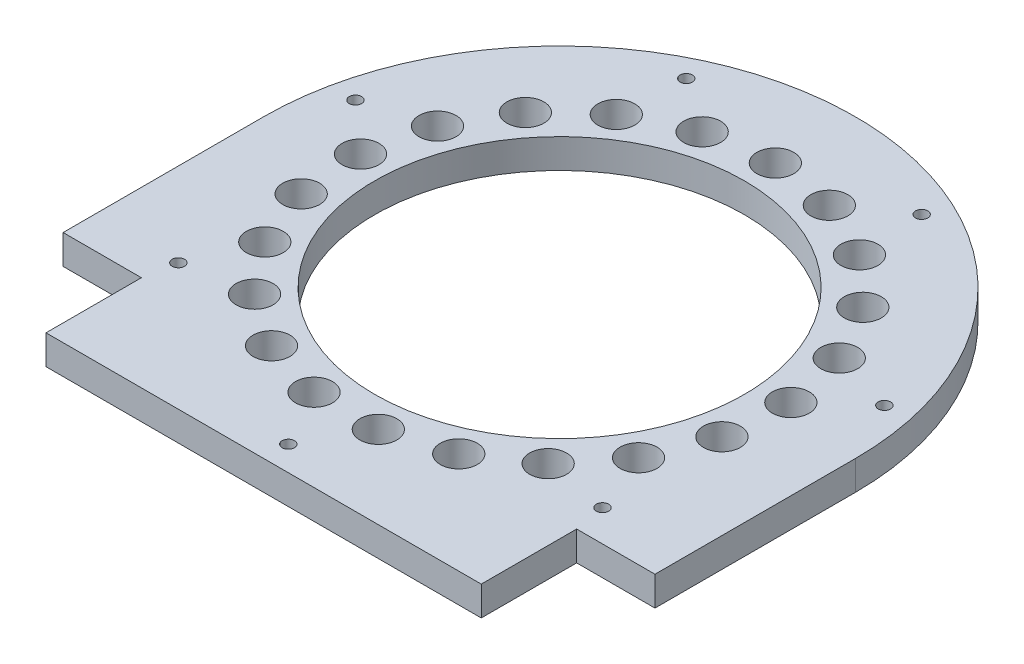
SolidWorks part; units mm, degrees
ref_plane "Front Plane" through (0, 0, 0) normal (0, 0, 1) x (1, 0, 0)
ref_plane "Top Plane" through (0, 0, 0) normal (0, 1, 0) x (1, 0, 0)
ref_plane "Right Plane" through (0, 0, 0) normal (1, 0, 0) x (0, 0, -1)
ref_axis "X Axis" through (-88.99, 0, 0) along (1, 0, 0)
ref_axis "Y Axiz" through (0, 0, 55) along (0, 0, -1)
ref_axis "Z Axis" through (0, 55, 0) along (0, -1, 0)
sketch "Sketch2" plane through (0, 0, 0) normal (0, 1, 0) x (1, 0, 0)
  line L0 (0, 0) -> (0, 35) construction
  line L1 (0, 0) -> (0, -44) construction
  line L2 (0, 0) -> (0, 48)
  line L13 (35.3, -48) -> (0, -48)
  line L14 (35.3, -32.5255) -> (35.3, -48)
  line L15 (48, -32.5255) -> (35.3, -32.5255)
  line L16 (48, 0) -> (48, -32.5255)
  line L17 (-48, 0) -> (48, 0)
  line L18 (-48, -32.5255) -> (-48, 0)
  line L19 (-35.3, -32.5255) -> (-48, -32.5255)
  line L20 (-35.3, -48) -> (-35.3, -32.5255)
  line L21 (0, -48) -> (-35.3, -48)
  circle A0 centre (0, 0) radius 48
  circle A1 centre (0, 35) radius 3
  circle A2 centre (10.3164, 33.445) radius 3
  circle A3 centre (19.7162, 28.9184) radius 3
  circle A4 centre (27.3641, 21.8221) radius 3
  circle A5 centre (32.5806, 12.7869) radius 3
  circle A6 centre (34.9021, 2.6156) radius 3
  circle A7 centre (34.1225, -7.7882) radius 3
  circle A8 centre (30.3109, -17.5) radius 3
  circle A9 centre (23.806, -25.6568) radius 3
  circle A10 centre (15.1859, -31.5339) radius 3
  circle A11 centre (5.2165, -34.6091) radius 3
  circle A12 centre (-5.2165, -34.6091) radius 3
  circle A13 centre (-15.1859, -31.5339) radius 3
  circle A14 centre (-23.806, -25.6568) radius 3
  circle A15 centre (-30.3109, -17.5) radius 3
  circle A16 centre (-34.1225, -7.7882) radius 3
  circle A24 centre (0, 0) radius 35 construction
  circle A27 centre (0, -44) radius 1
  circle A28 centre (-34.4006, -27.4336) radius 1
  circle A29 centre (-42.8968, 9.7909) radius 1
  circle A30 centre (-19.0909, 39.6426) radius 1
  circle A31 centre (19.0909, 39.6426) radius 1
  circle A32 centre (42.8968, 9.7909) radius 1
  circle A33 centre (34.4006, -27.4336) radius 1
  circle A35 centre (-34.9021, 2.6156) radius 3
  circle A36 centre (-32.5806, 12.7869) radius 3
  circle A37 centre (-27.3641, 21.8221) radius 3
  circle A38 centre (-19.7162, 28.9184) radius 3
  circle A39 centre (-10.3164, 33.445) radius 3
  circle A40 centre (0, 0) radius 44 construction
  circle A42 centre (0, 35) radius 5 construction
  circle A43 centre (0, 0) radius 40 construction
  circle A45 centre (0, 0) radius 30
  point P38 (0, 0)
  point P51 (0, 0)
  point P54 (0, 0)
  point P59 (0, 0)
  dimension "D1" = 6
  dimension "D3" = 96
  dimension "D6" = 7
  dimension "D7" = 35
  dimension "D4" = 44
  dimension "D5" = 2
  dimension "D8" = 10
  dimension "60" = 60
  dimension "D2" = 21
extrude "Boss-Extrude2" add sketch "Sketch2" along normal blind 4.7625 contours A45 L17 A6 A0 L2 A1 A32 A31 A5 A4 A3 A2 | A45 L17 A35 A0 A6 A33 A28 A27 A16 A15 A14 A13 A12 A11 A10 A9 A8 A7 | A0 L15 L16 | A0 L13 L14 | A0 L20 L21 | A0 L18 L19 | A45 L2 A1 A0 L17 A35 A39 A38 A37 A36 A30 A29 region at (-25.6428, 0, -25.9093) region at (25.6428, 0, -25.9093) region at (31.7164, 0, 1.0733) region at (44.2953, 0, 24.625) region at (-44.2953, 0, 24.625) region at (26.7848, 0, 43.5217) region at (-26.7848, 0, 43.5217)
